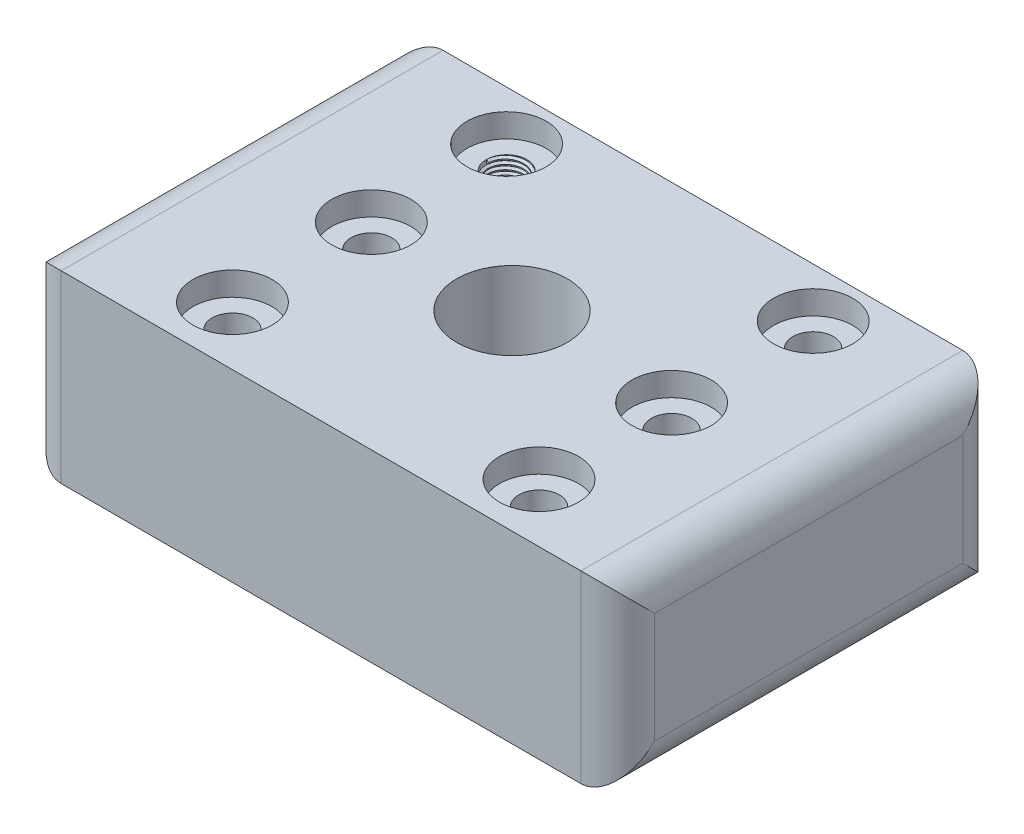
SolidWorks part; units mm, degrees
ref_plane "Front Plane" through (0, 0, 0) normal (0, 0, 1) x (1, 0, 0)
ref_plane "Top Plane" through (0, 0, 0) normal (0, 1, 0) x (1, 0, 0)
ref_plane "Right Plane" through (0, 0, 0) normal (1, 0, 0) x (0, 0, -1)
sketch "Sketch2" plane through (0, 0, 0) normal (0, 1, 0) x (1, 0, 0)
  line L1 (-80.4962, 51.7976) -> (80.4962, 51.7976)
  line L2 (-80.4962, 51.7976) -> (-80.4962, -51.7976)
  line L3 (-80.4962, -51.7976) -> (80.4962, -51.7976)
  line L4 (80.4962, 51.7976) -> (80.4962, -51.7976)
  line L5 (-80.4962, 51.7976) -> (80.4962, -51.7976) construction
  line L6 (-80.4962, -51.7976) -> (80.4962, 51.7976) construction
  point P0 (0, 0)
extrude "Boss-Extrude1" add sketch "Sketch2" along normal blind 50
sketch "Sketch3" plane through (0, 50, 0) normal (0, 1, 0) x (1, 0, 0)
  circle A0 centre (0, 0) radius 15
extrude "Cut-Extrude1" cut sketch "Sketch3" against normal blind 50
hole_wizard "CBORE for M10 Hex Head Bolt1" positions "Sketch4" profile "Sketch5" counterbore size "M10" standard "ISO" end condition through all
sketch "Sketch4" plane through (0, 50, 0) normal (0, 1, 0) x (1, 0, 0)
  point P0 (0, 0)
  point P4 (-39.8745, 1.7124)
  point P6 (43.2993, 0)
  point P8 (43.2993, 38.4068)
  point P10 (-39.8745, 38.4068)
  point P12 (-39.8745, -35.9605)
  point P14 (43.2993, -35.9605)
sketch "Sketch5" plane through (0, 50, 0) normal (1, 0, 0) x (0, 0, 1)
  line L0 (0, 0) -> (0, 50)
  line L1 (0, 50) -> (5.5, 50)
  line L3 (5.5, 50) -> (5.5, 6.4)
  line L4 (5.5, 6.4) -> (10.7375, 6.4)
  line L5 (10.7375, 6.4) -> (10.7375, 0)
  line L7 (10.7375, 0) -> (0, 0)
  line L11 (0, -6.35) -> (0, 107.95) construction
  dimension "Thru Hole Dia." = 11
  dimension "Thru Hole Depth" = 50
  dimension "C'Bore Dia." = 21.475
  dimension "C'Bore Depth" = 6.4
thread "Thread2" pitch 1.25 method extrude profile "Thread Profile3" start angle 0, offset 0, length 10, pitch 1.25, diameter 11
ref_plane "Plane3" through (-45.3745, 43.6, -38.4068) normal (0, 0, 1) x (-1, 0, 0)
sketch "Thread Profile3" plane through (-45.3745, 43.6, -38.4068) normal (0, 0, 1) x (-1, 0, 0)
  line L0 (0, 0) -> (0, 1.25) construction
  line L11 (0, 0) -> (0, 1.0937)
  line L12 (0, 1.0937) -> (-0.6766, 0.7031)
  line L13 (-0.6766, 0.7031) -> (-0.6766, 0.3906)
  line L15 (-0.6766, 0.3906) -> (0, 0)
  line L17 (-0.6766, 0.5469) -> (0, 0.5469) construction
  point P2 (0, 0)
  dimension "Pitch" = 1.25
  dimension "Profile_Angle" = 60
  dimension "Profile_Land" = 0.3125
  dimension "Profile_Height" = 0.6766
fillet "Fillet3" radius 10 8 edges at (80.4962, 25, -51.7976) (80.4962, 25, 51.7976) (80.4962, 0, 0) (80.4962, 50, 0) (-80.4962, 50, 0) (-80.4962, 0, 0) (-80.4962, 25, 51.7976) (-80.4962, 25, -51.7976)
